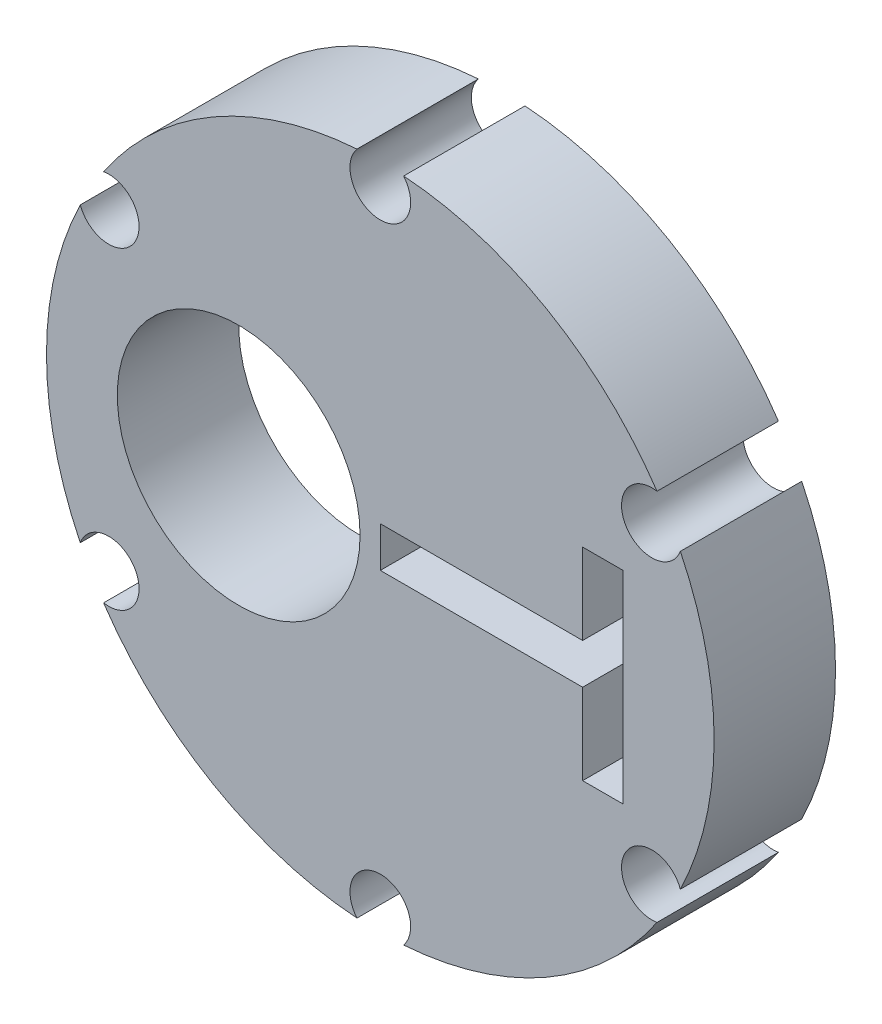
SolidWorks part; units mm, degrees
material "ABS"
ref_plane "Front Plane" through (0, 0, 0) normal (0, 0, 1) x (1, 0, 0)
ref_plane "Top Plane" through (0, 0, 0) normal (0, 1, 0) x (1, 0, 0)
ref_plane "Right Plane" through (0, 0, 0) normal (1, 0, 0) x (0, 0, -1)
sketch "Sketch1" plane through (0, 0, 0) normal (0, 0, 1) x (1, 0, 0)
  circle A0 centre (0, 0) radius 16.5
  dimension "D1" = 33
extrude "Boss-Extrude1" add sketch "Sketch1" along normal blind 6
sketch "Sketch2" plane through (0, 0, 6) normal (0, 0, 1) x (1, 0, 0)
  circle A0 centre (0, 15.5) radius 1.5
  circle A1 centre (13.4234, 7.75) radius 1.5
  circle A2 centre (13.4234, -7.75) radius 1.5
  circle A3 centre (0, -15.5) radius 1.5
  circle A4 centre (-13.4234, -7.75) radius 1.5
  circle A5 centre (-13.4234, 7.75) radius 1.5
  point P15 (0, 0)
  dimension "D1" = 3
  dimension "D2" = 15.5
  dimension "D3" = 6
extrude "Cut-Extrude1" cut sketch "Sketch2" against normal through all
sketch "Sketch3" plane through (0, 0, 6) normal (0, 0, 1) x (1, 0, 0)
  line L0 (-7, 0) -> (0, 0) construction
  circle A0 centre (-7, 0) radius 6
  dimension "D1" = 12
  dimension "D3" = 7
extrude "Cut-Extrude2" cut sketch "Sketch3" against normal through all
sketch "Sketch5" plane through (0, 0, 6) normal (0, 0, 1) x (1, 0, 0)
  line L1 (12, 5) -> (10, 5)
  line L2 (12, 5) -> (12, -5)
  line L3 (12, -5) -> (10, -5)
  line L4 (10, 5) -> (10, 1)
  line L5 (10, -1) -> (10, -5)
  line L6 (0, 1) -> (10, 1)
  line L7 (0, 1) -> (0, -1)
  line L8 (0, -1) -> (10, -1)
  point P10 (0, 0)
  dimension "D1" = 10
  dimension "D2" = 2
extrude "Cut-Extrude3" cut sketch "Sketch5" against normal through all
equation "\"smallPulleyTeeth\"= 15"
equation "\"largePulleyTeeth\"= 30"
equation "\"eighthThick\"= 2.9mm"
equation "\"sixteenthThick\"= 1.7mm"
equation "\"wheelEighthThick\"=3.0mm"
equation "\"quarterThick\"=6.0mm"
equation "\"OD\"= 145mm"
equation "\"puckAngle\"= 60.5deg"
equation "\"puckDiam\"= 76.5mm"
equation "\"axlePress\"= 5.9mm"
equation "\"D1@Boss-Extrude1\"=\"quarterThick\""
